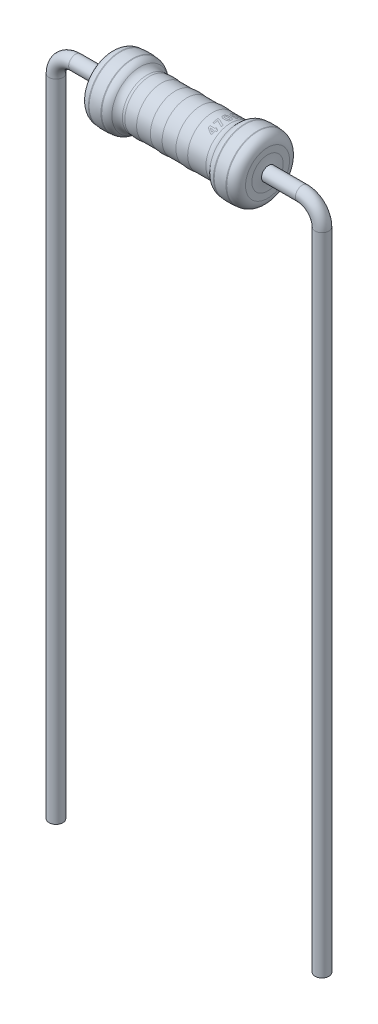
SolidWorks part; units mm, degrees
material "Plain Carbon Steel"
ref_plane "Front Plane" through (0, 0, 0) normal (0, 0, 1) x (1, 0, 0)
ref_plane "Top Plane" through (0, 0, 0) normal (0, 1, 0) x (1, 0, 0)
ref_plane "Right Plane" through (0, 0, 0) normal (1, 0, 0) x (0, 0, -1)
sketch "Sketch1" plane through (0, 0, 0) normal (0, 0, 1) x (1, 0, 0)
  line L0 (-4.33, 0) -> (4.33, 0)
  line L1 (-5.08, -0.75) -> (-5.08, -25.4)
  line L2 (5.08, -0.75) -> (5.08, -25.4)
  line L3 (-5.08, -25.4) -> (5.08, -25.4) construction
  line L4 (0, 0) -> (0, -25.4) construction
  arc A0 (-4.33, 0) -> (-5.08, -0.75) centre (-4.33, -0.75) ccw
  arc A1 (4.33, 0) -> (5.08, -0.75) centre (4.33, -0.75) cw
  dimension "D2" = 0.75
  dimension "D1" = 10.16
  dimension "D3" = 25.4
ref_plane "Plane1" through (-5.08, -25.4, 0) normal (0, -1, 0) x (-1, 0, 0)
sketch "Sketch2" plane through (-5.08, -25.4, 0) normal (0, -1, 0) x (-1, 0, 0)
  circle A0 centre (0, 0) radius 0.265
  dimension "D1" = 0.53
sweep "Sweep1" add profiles "Sketch2" path "Sketch1"
sketch "Sketch3" plane through (0, 0, 0) normal (0, 0, 1) x (1, 0, 0)
  line L0 (-3, 0) -> (3, 0)
  line L5 (-3, 0) -> (-3, 1.2)
  line L6 (3, 0) -> (3, 1.2)
  line L7 (-3, 1.2) -> (-1.8, 1.2)
  line L8 (3, 1.2) -> (1.8, 1.2)
  line L9 (-1.8, 1.2) -> (-1.8, 0.95)
  line L10 (-1.8, 0.95) -> (1.8, 0.95)
  line L11 (1.8, 0.95) -> (1.8, 1.2)
  line L12 (0, 0) -> (0, 0.95) construction
  dimension "D1" = 6
  dimension "D2" = 1.2
  dimension "D3" = 3.6
  dimension "D4" = 0.95
  dimension "D5" = 0.25
revolve "Revolve1" add sketch "Sketch3" angle 360 about L0
fillet "Fillet-1" radius 0.35 2 edges at (1.8, 0, 1.2) (-1.8, 0, 1.2)
fillet "Fillet-2" radius 0.36 4 edges at (3, 0, 1.2) (-3, 0, 1.2) (1.8, 0, 0.95) (-1.8, 0, 0.95)
sketch "Sketch5" plane through (0, 0, 0) normal (0, 0, 1) x (1, 0, 0)
  line L0 (-2.64, -1.2) -> (-2.1354, -1.2) construction
  line L5 (-2.3877, -1.2) -> (-2.3877, 0) construction
  line L10 (-3, 1.2) -> (-1.8, 1.2) construction
  line L15 (-1.05, 0.95) -> (-0.525, 0.95) construction
  line L16 (-3, 0) -> (3, 0) construction
  line L17 (-2.6127, 1.2) -> (-2.1627, 1.2) construction
  line L18 (-2.6127, 1.2) -> (-2.6127, 0) construction
  line L19 (-2.6127, 0) -> (-2.1627, 0) construction
  line L20 (-2.1627, 1.2) -> (-2.1627, 0) construction
  line L21 (-1.8, 0.95) -> (1.8, 0.95) construction
  line L22 (2.6127, 1.2) -> (2.1627, 1.2) construction
  line L23 (2.6127, 1.2) -> (2.6127, 0) construction
  line L24 (2.6127, 0) -> (2.1627, 0) construction
  line L25 (2.1627, 1.2) -> (2.1627, 0) construction
  line L26 (-1.05, 0.95) -> (-1.5, 0.95) construction
  line L27 (-1.05, 0.95) -> (-1.05, 0) construction
  line L28 (-1.05, 0) -> (-1.5, 0) construction
  line L29 (-1.5, 0.95) -> (-1.5, 0) construction
  line L30 (-2.3877, 1.2) -> (-2.3877, 1.22) construction
  line L31 (-0.075, 0.95) -> (-0.525, 0.95) construction
  line L32 (-0.075, 0.95) -> (-0.075, 0) construction
  line L33 (-0.075, 0) -> (-0.525, 0) construction
  line L34 (-0.525, 0.95) -> (-0.525, 0) construction
  line L35 (-1.275, 0.95) -> (-1.275, 0.97) construction
  line L36 (-0.3, 0.95) -> (-0.3, 0.97) construction
  line L37 (2.3877, 1.2) -> (2.3877, 1.22) construction
  line L39 (2.1354, -1.2) -> (2.64, -1.2) construction
  line L41 (2.3877, -1.2) -> (2.3877, 0) construction
  line L44 (3, 1.2) -> (1.8, 1.2) construction
  line L46 (-0.075, 0.95) -> (0.45, 0.95) construction
  line L48 (-3, 0) -> (-3, 0.6)
  line L49 (-3, 0) -> (-3, 1.2) construction
  line L50 (-3, 0) -> (-3.05, 0)
  line L51 (-3.05, 0) -> (-3.05, 0.2)
  line L52 (3, 0) -> (3.05, 0)
  line L53 (3.05, 0) -> (3.05, 0.2)
  line L54 (3, 0) -> (3, 0.6)
  line L55 (3, 0) -> (3, 1.2) construction
  line L56 (-1.05, 0) -> (-0.525, 0) construction
  line L58 (-0.075, 0) -> (0.45, 0) construction
  line L59 (0.45, 0) -> (0.45, 0.95) construction
  line L60 (0.45, 0) -> (0.9, 0) construction
  line L61 (0.9, 0) -> (0.9, 0.95) construction
  line L62 (1.5946, 0.95) -> (-1.5946, 0.95) construction
  line L63 (0.9, 0.95) -> (0.45, 0.95) construction
  line L64 (0.675, 0.95) -> (0.675, 0.97) construction
  arc A0 (-2.6127, 1.2) -> (-2.1627, 1.2) centre (-2.3877, -0.0556) cw construction
  arc A1 (-1.5, 0.95) -> (-1.05, 0.95) centre (-1.275, -0.3056) cw construction
  arc A2 (-0.525, 0.95) -> (-0.075, 0.95) centre (-0.3, -0.3056) cw construction
  arc A3 (2.1627, 1.2) -> (2.6127, 1.2) centre (2.3877, -0.0556) cw construction
  arc A6 (-3, 0.6) -> (-3.05, 0.2) centre (-4.625, 0.6) cw
  arc A7 (3.05, 0.2) -> (3, 0.6) centre (4.625, 0.6) cw
  arc A8 (0.45, 0.95) -> (0.9, 0.95) centre (0.675, -0.3056) cw construction
  dimension "D4" = 0.02
  dimension "D5" = 0.05
  dimension "D7" = 0.6
  dimension "D2" = 1.5
  dimension "D3" = 2.4
  dimension "D1" = 0.45
  dimension "D6" = 0.2
revolve "Revolve Ends" add sketch "Sketch5" angle 360 about L19
sketch "Sketch12" plane through (0, 0, 0) normal (0, 0, 1) x (1, 0, 0)
  line L0 (-2.6127, 0) -> (-2.1627, 0) construction
  line L1 (-2.6127, 0) -> (-2.1627, 0)
  line L2 (-2.6127, 1.2) -> (-2.6127, 0) construction
  line L3 (-2.6127, 1.2) -> (-2.6127, 0)
  line L4 (-2.1627, 1.2) -> (-2.1627, 0) construction
  line L5 (-2.1627, 1.2) -> (-2.1627, 0)
  arc A0 (-2.1627, 1.2) -> (-2.6127, 1.2) centre (-2.3877, -0.0556) ccw construction
  arc A1 (-2.1627, 1.2) -> (-2.6127, 1.2) centre (-2.3877, -0.0556) ccw
revolve "Revolve BAND 1" add sketch "Sketch12" angle 360 about L19
sketch "Sketch7" plane through (0, 0, 0) normal (0, 0, 1) x (1, 0, 0)
  line L0 (-1.05, 0) -> (-1.5, 0) construction
  line L1 (-1.05, 0.95) -> (-1.05, 0) construction
  line L2 (-1.5, 0.95) -> (-1.5, 0) construction
  line L3 (-1.05, 0.95) -> (-1.05, 0)
  line L4 (-1.5, 0.95) -> (-1.5, 0)
  line L5 (-1.05, 0) -> (-1.5, 0)
  arc A0 (-1.05, 0.95) -> (-1.5, 0.95) centre (-1.275, -0.3056) ccw construction
  arc A1 (-1.05, 0.95) -> (-1.5, 0.95) centre (-1.275, -0.3056) ccw
revolve "Revolve BAND 2" add sketch "Sketch7" angle 360 about L28
sketch "Sketch8" plane through (0, 0, 0) normal (0, 0, 1) x (1, 0, 0)
  line L0 (-0.075, 0.95) -> (-0.075, 0) construction
  line L1 (-0.075, 0) -> (-0.525, 0) construction
  line L2 (-0.525, 0.95) -> (-0.525, 0) construction
  line L3 (-0.075, 0.95) -> (-0.075, 0)
  line L4 (-0.075, 0) -> (-0.525, 0)
  line L5 (-0.525, 0.95) -> (-0.525, 0)
  arc A0 (-0.075, 0.95) -> (-0.525, 0.95) centre (-0.3, -0.3056) ccw construction
  arc A1 (-0.075, 0.95) -> (-0.525, 0.95) centre (-0.3, -0.3056) ccw
revolve "Revolve BAND 3" add sketch "Sketch8" angle 360 about L33
sketch "Sketch9" plane through (0, 0, 0) normal (0, 0, 1) x (1, 0, 0)
  line L0 (0.9, 0) -> (0.9, 0.95) construction
  line L1 (0.45, 0) -> (0.45, 0.95) construction
  line L2 (0.45, 0) -> (0.9, 0) construction
  line L3 (0.9, 0) -> (0.9, 0.95)
  line L4 (0.45, 0) -> (0.45, 0.95)
  line L5 (0.45, 0) -> (0.9, 0)
  arc A0 (0.9, 0.95) -> (0.45, 0.95) centre (0.675, -0.3056) ccw construction
  arc A1 (0.9, 0.95) -> (0.45, 0.95) centre (0.675, -0.3056) ccw
revolve "Revolve BAND 4" add sketch "Sketch9" angle 360 about L60
sketch "Sketch11" plane through (0, 0, 0) normal (0, 0, 1) x (1, 0, 0)
  line L0 (2.6127, 1.2) -> (2.6127, 0) construction
  line L1 (2.1627, 1.2) -> (2.1627, 0) construction
  line L2 (2.6127, 0) -> (2.1627, 0) construction
  line L3 (2.6127, 1.2) -> (2.6127, 0)
  line L4 (2.1627, 1.2) -> (2.1627, 0)
  line L5 (2.6127, 0) -> (2.1627, 0)
  arc A0 (2.6127, 1.2) -> (2.1627, 1.2) centre (2.3877, -0.0556) ccw construction
  arc A1 (2.6127, 1.2) -> (2.1627, 1.2) centre (2.3877, -0.0556) ccw
revolve "Revolve5" add sketch "Sketch11" angle 360 about L24
ref_plane "Plane2" through (0, 2, 0) normal (0, 1, 0) x (1, 0, 0)
sketch "Sketch6" plane through (0, 2, 0) normal (0, 1, 0) x (1, 0, 0)
  line L0 (0, 0) -> (1.5, 0) construction
  line L1 (1.5, 1) -> (1.5, -1) construction
  text T0 "470Ω" font "Calibri" height 0.3
  dimension "D1" = 1.5
  dimension "D2" = 2
wrap "Wrap1" sketch "Sketch6" wrap type scribe source sketch "Sketch6" face at (1.5946, 0, 0.95)
